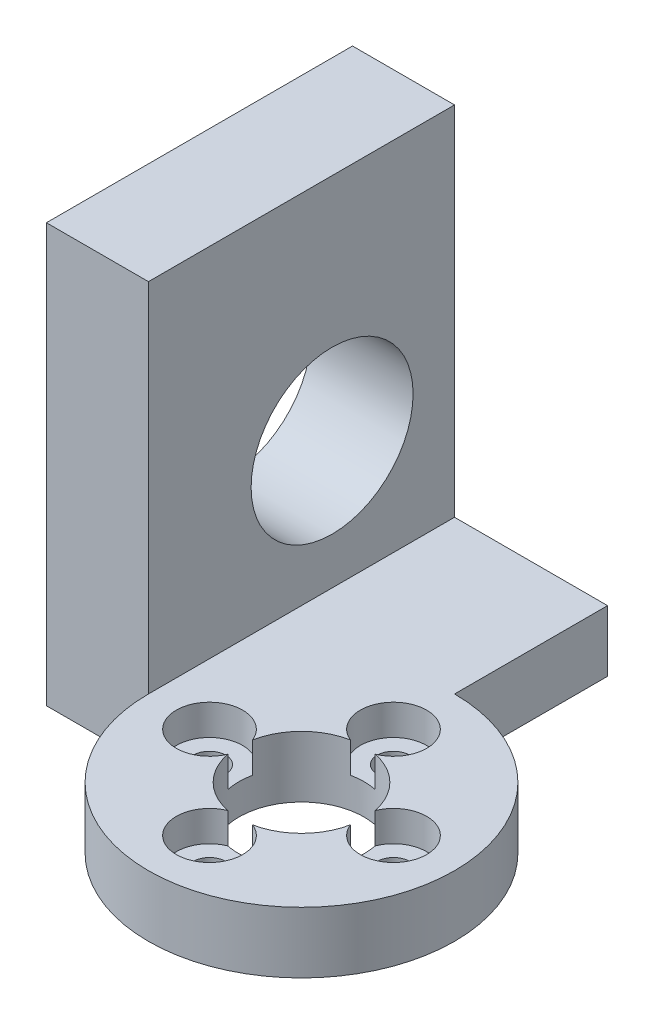
SolidWorks part; units mm, degrees
ref_plane "Front Plane" through (0, 0, 0) normal (0, 0, 1) x (1, 0, 0)
ref_plane "Top Plane" through (0, 0, 0) normal (0, 1, 0) x (1, 0, 0)
ref_plane "Right Plane" through (0, 0, 0) normal (1, 0, 0) x (0, 0, -1)
sketch "Sketch1" plane through (0, 0, 0) normal (0, 1, 0) x (1, 0, 0)
  circle A0 centre (0, 0) radius 15
  dimension "D1" = 30
extrude "Boss-Extrude1" add sketch "Sketch1" along normal blind 6
sketch "Sketch2" plane through (0, 6, 0) normal (0, 1, 0) x (1, 0, 0)
  circle A0 centre (0, 0) radius 6.125
  dimension "D1" = 12.25
extrude "Cut-Extrude1" cut sketch "Sketch2" against normal up to next
hole_wizard "CBORE for M3 SHCS2" positions "Sketch3" profile "Sketch5" counterbore size "M3" standard "ANSI Metric" end condition up to next
sketch "Sketch3" plane through (0, 6, 0) normal (0, 1, 0) x (1, 0, 0)
  point P0 (0, 9.017)
  dimension "D1" = 9.017
sketch "Sketch5" plane through (0, 6, -9.017) normal (1, 0, 0) x (0, 0, 1)
  line L0 (0, 0) -> (0, 6)
  line L1 (0, 6) -> (1.6, 6)
  line L3 (1.6, 6) -> (1.6, 3)
  line L4 (1.6, 3) -> (3.25, 3)
  line L5 (3.25, 3) -> (3.25, 0)
  line L7 (3.25, 0) -> (0, 0)
  line L11 (0, -6.35) -> (0, 107.95) construction
  dimension "Thru Hole Dia." = 3.2
  dimension "Thru Hole Depth" = 6
  dimension "C'Bore Dia." = 6.5
  dimension "C'Bore Depth" = 3
pattern_circular "CirPattern1" count 4 over 360 about axis through (0, -0.001, 0) along (0, 1, 0) of "CBORE for M3 SHCS2"
sketch "Sketch6" plane through (0, 6, 0) normal (0, 1, 0) x (1, 0, 0)
  line L0 (-25, 0) -> (-25, 15)
  line L1 (-25, 15) -> (0, 15)
  line L2 (-25, 0) -> (-15, 0)
  circle A0 centre (0, 0) radius 15 construction
  arc A1 (0, 15) -> (-15, 0) centre (0, 0) ccw
  dimension "D1" = 25
extrude "Boss-Extrude2" add sketch "Sketch6" against normal up to surface (6 mm away) and the other way blind 35 up to face at (9.017, 0, 1.6)
sketch "Sketch7" plane through (-25, 0, 0) normal (-1, 0, 0) x (0, 0, 1)
  line L4 (-15, 6) -> (0, 6)
  line L5 (-15, 41) -> (-15, 6)
  line L6 (0, 41) -> (-15, 41)
  line L7 (0, 6) -> (0, 41)
  line L8 (-15, 6) -> (0, 6)
  line L9 (-15, 41) -> (-15, 6)
  line L10 (0, 41) -> (-15, 41)
  line L11 (0, 6) -> (0, 41)
  dimension "D1" = 0
extrude "Cut-Extrude2" cut sketch "Sketch7" against normal up to next from vertex starting at point (-15, 41, 0)
sketch "Sketch9" plane through (0, 0, -15) normal (0, 0, -1) x (-1, 0, 0)
  line L6 (15, 41) -> (15, 6)
  line L7 (15, 6) -> (0, 6)
  line L8 (0, 6) -> (0, 0)
  line L9 (0, 0) -> (25, 0)
  line L10 (25, 0) -> (25, 41)
  line L11 (25, 41) -> (15, 41)
  line L12 (15, 41) -> (15, 6)
  line L13 (15, 6) -> (0, 6)
  line L14 (0, 6) -> (0, 0)
  line L15 (0, 0) -> (25, 0)
  line L16 (25, 0) -> (25, 41)
  line L17 (25, 41) -> (15, 41)
  dimension "D1" = 0
extrude "Boss-Extrude3" add sketch "Sketch9" along normal blind 15
sketch "Sketch8" plane through (-15, 0, 0) normal (1, 0, 0) x (0, 0, -1)
  line L0 (0, 0) -> (0, 37.894) construction
  line L1 (8, 0) -> (8, 37.894) construction
  line L2 (-15, 0) -> (15, 0) construction
  line L3 (18, 0) -> (18, 37.894) construction
  line L4 (30, 6) -> (15, 6) construction
  circle A0 centre (18, 18.5) radius 10 construction
  circle A1 centre (18, 18.5) radius 7.9375
  dimension "D3" = 12.5
  dimension "D4" = 15.875
  dimension "D1" = 8
  dimension "D2" = 10
extrude "Cut-Extrude3" cut sketch "Sketch8" against normal up to next
